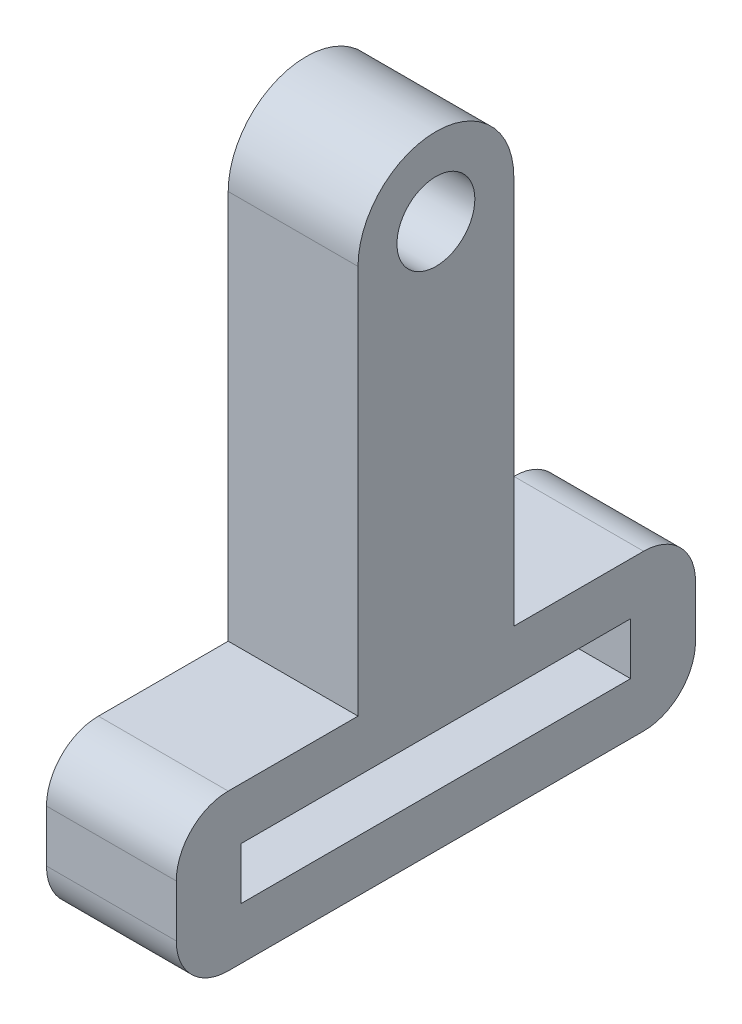
SolidWorks part; units mm, degrees
ref_plane "Alzado" through (0, 0, 0) normal (0, 0, 1) x (1, 0, 0)
ref_plane "Planta" through (0, 0, 0) normal (0, 1, 0) x (1, 0, 0)
ref_plane "Vista lateral" through (0, 0, 0) normal (1, 0, 0) x (0, 0, -1)
sketch "Croquis1" plane through (0, 0, 0) normal (1, 0, 0) x (0, 0, -1)
  line L2 (-10, 1) -> (-10, -1)
  line L3 (-8, -3) -> (8, -3)
  line L4 (10, 1) -> (10, -1)
  line L5 (-10, 3) -> (10, -3) construction
  line L6 (-10, -3) -> (10, 3) construction
  line L7 (-7.5, 1) -> (7.5, 1)
  line L8 (-7.5, 1) -> (-7.5, -1)
  line L9 (-7.5, -1) -> (7.5, -1)
  line L10 (7.5, 1) -> (7.5, -1)
  line L11 (-7.5, 1) -> (7.5, -1) construction
  line L12 (-7.5, -1) -> (7.5, 1) construction
  line L15 (-10, 3) -> (10, 3) construction
  line L27 (-3, 3) -> (-8, 3)
  line L28 (3, 3) -> (8, 3)
  line L35 (0, 3) -> (0, 18) construction
  line L36 (-3, 18) -> (-3, 3)
  line L39 (3, 18) -> (3, 3)
  circle A1 centre (0, 18) radius 1.5
  arc A2 (3, 18) -> (-3, 18) centre (0, 18) ccw
  arc A3 (8, -3) -> (10, -1) centre (8, -1) ccw
  arc A4 (8, 3) -> (10, 1) centre (8, 1) cw
  arc A5 (-10, -1) -> (-8, -3) centre (-8, -1) ccw
  arc A6 (-8, 3) -> (-10, 1) centre (-8, 1) ccw
  point P0 (0, 0)
  point P6 (0, 0)
  dimension "D18" = 6
  dimension "D17" = 3
  dimension "D6" = 2
  dimension "D2" = 20
  dimension "D3" = 2
  dimension "D4" = 15
  dimension "D5" = 6
  dimension "D16" = 15
  dimension "D23" = 2
extrude "Saliente-Extruir1" add sketch "Croquis1" along normal mid plane 5
